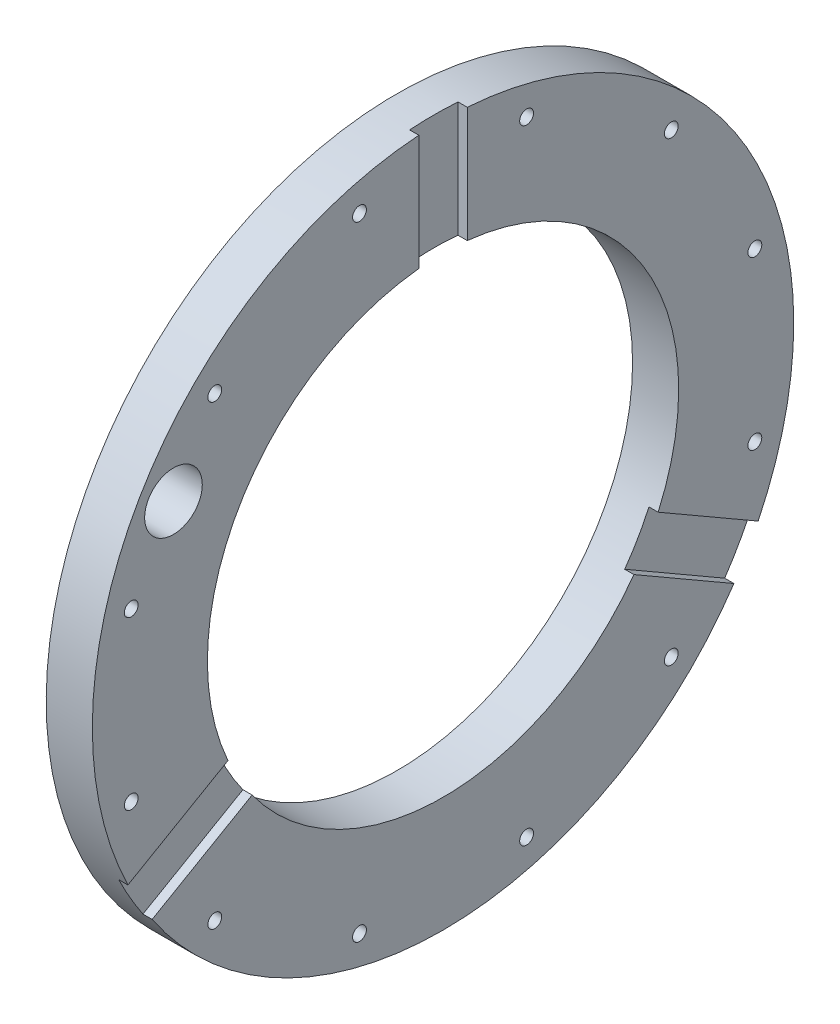
SolidWorks part; units mm, degrees
material "Teck"
ref_plane "Plan de face" through (0, 0, 0) normal (0, 0, 1) x (1, 0, 0)
ref_plane "Plan de dessus" through (0, 0, 0) normal (0, 1, 0) x (1, 0, 0)
ref_plane "Plan de droite" through (0, 0, 0) normal (1, 0, 0) x (0, 0, -1)
sketch "Esquisse1" plane through (0, 0, 0) normal (1, 0, 0) x (0, 0, -1)
  circle A0 centre (0, 0) radius 51.1
  circle A1 centre (0, 0) radius 76.05
  dimension "D1" = 102.2
  dimension "D2" = 152.1
extrude "Boss.-Extru.1" add sketch "Esquisse1" along normal blind 10
sketch "Esquisse2" plane through (10, 0, 0) normal (1, 0, 0) x (0, 0, -1)
  line L0 (0, 0) -> (0, 93.2779) construction
  line L1 (5.25, 85.8093) -> (-5.25, 85.8093)
  line L2 (5.25, 85.8093) -> (5.25, 36.2596)
  line L3 (5.25, 36.2596) -> (-5.25, 36.2596)
  line L4 (-5.25, 85.8093) -> (-5.25, 36.2596)
  dimension "D1" = 10.5
extrude "Enlèv. mat.-Extru.1" cut sketch "Esquisse2" against normal blind 2
pattern_circular "Répétition circulaire1" count 3 over 360 about axis through (0, 0, 0) along (1, 0, 0) of "Enlèv. mat.-Extru.1"
sketch "Esquisse3" plane through (10, 0, 0) normal (1, 0, 0) x (0, 0, -1)
  line L0 (0, 0) -> (0, 80.0302) construction
  line L1 (0, 0) -> (18.1173, 67.6148) construction
  circle A0 centre (18.1173, 67.6148) radius 1.5
  circle A1 centre (0, 0) radius 70 construction
  dimension "D1" = 140
  dimension "D2" = 3
  dimension "D3" = 15
extrude "Enlèv. mat.-Extru.2" cut sketch "Esquisse3" against normal through all
pattern_circular "Répétition circulaire2" count 12 over 360 about axis through (0, 0, 0) along (1, 0, 0) of "Enlèv. mat.-Extru.2"
sketch "Esquisse4" plane through (10, 0, 0) normal (1, 0, 0) x (0, 0, -1)
  line L0 (0, 0) -> (-58.4567, 33.75) construction
  line L1 (0, 0) -> (0, 41.2211) construction
  circle A0 centre (-58.4567, 33.75) radius 6.25
  dimension "D1" = 12.5
  dimension "D2" = 67.5
  dimension "D3" = 60
extrude "Enlèv. mat.-Extru.3" cut sketch "Esquisse4" against normal blind 10
